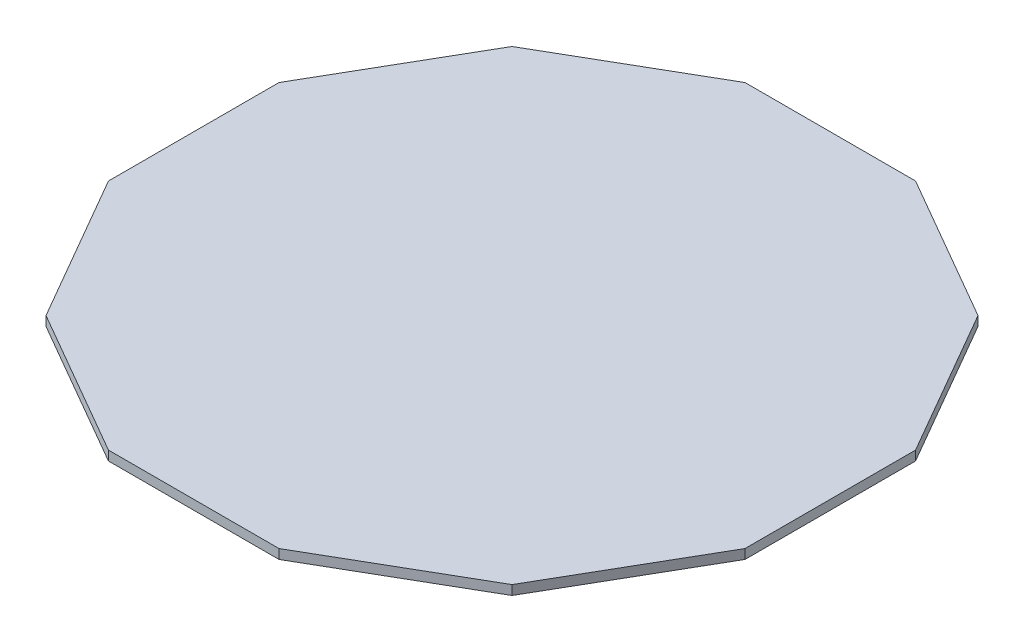
SolidWorks part; units mm, degrees
ref_plane "Front Plane" through (0, 0, 0) normal (0, 0, 1) x (1, 0, 0)
ref_plane "Top Plane" through (0, 0, 0) normal (0, 1, 0) x (1, 0, 0)
ref_plane "Right Plane" through (0, 0, 0) normal (1, 0, 0) x (0, 0, -1)
sketch "Sketch1" plane through (0, 0, 0) normal (0, 1, 0) x (1, 0, 0)
  line L0 (26.296, 98.1381) -> (-26.296, 98.1381)
  line L1 (-26.296, 98.1381) -> (-71.842, 71.842)
  line L2 (-71.842, 71.842) -> (-98.1381, 26.296)
  line L3 (-98.1381, 26.296) -> (-98.1381, -26.296)
  line L4 (-98.1381, -26.296) -> (-71.842, -71.842)
  line L5 (-71.842, -71.842) -> (-26.296, -98.1381)
  line L6 (-26.296, -98.1381) -> (26.296, -98.1381)
  line L7 (26.296, -98.1381) -> (71.842, -71.842)
  line L8 (71.842, -71.842) -> (98.1381, -26.296)
  line L9 (98.1381, -26.296) -> (98.1381, 26.296)
  line L10 (98.1381, 26.296) -> (71.842, 71.842)
  line L11 (71.842, 71.842) -> (26.296, 98.1381)
  circle A0 centre (0, 0) radius 101.6
  point P14 (-33.3696, 79.6047)
  point P16 (-14.0714, 86.592)
  point P17 (129.0013, 95.5756)
  point P18 (221.1667, -83.4317)
  point P19 (0, 0)
  point P20 (0, 0)
  point P21 (0, 0)
  point P22 (0, 0)
  point P23 (0, 0)
  point P24 (0, 0)
  point P25 (0, 0)
  point P26 (80.4231, -25.8699)
  point P27 (77.0958, 3.0774)
  point P28 (51.4758, 42.0065)
  point P29 (0, 0)
  point P30 (0, 0)
  point P31 (0, 0)
  point P32 (0, 0)
  point P33 (13.2915, 100.7268)
  dimension "D1" = 203.2
extrude "Boss-Extrude1" add sketch "Sketch1" against normal blind 2.921 contours L10 L11 L0 L1 L2 L3 L4 L5 L6 L7 L8 L9 region at (0, 0, 0)
